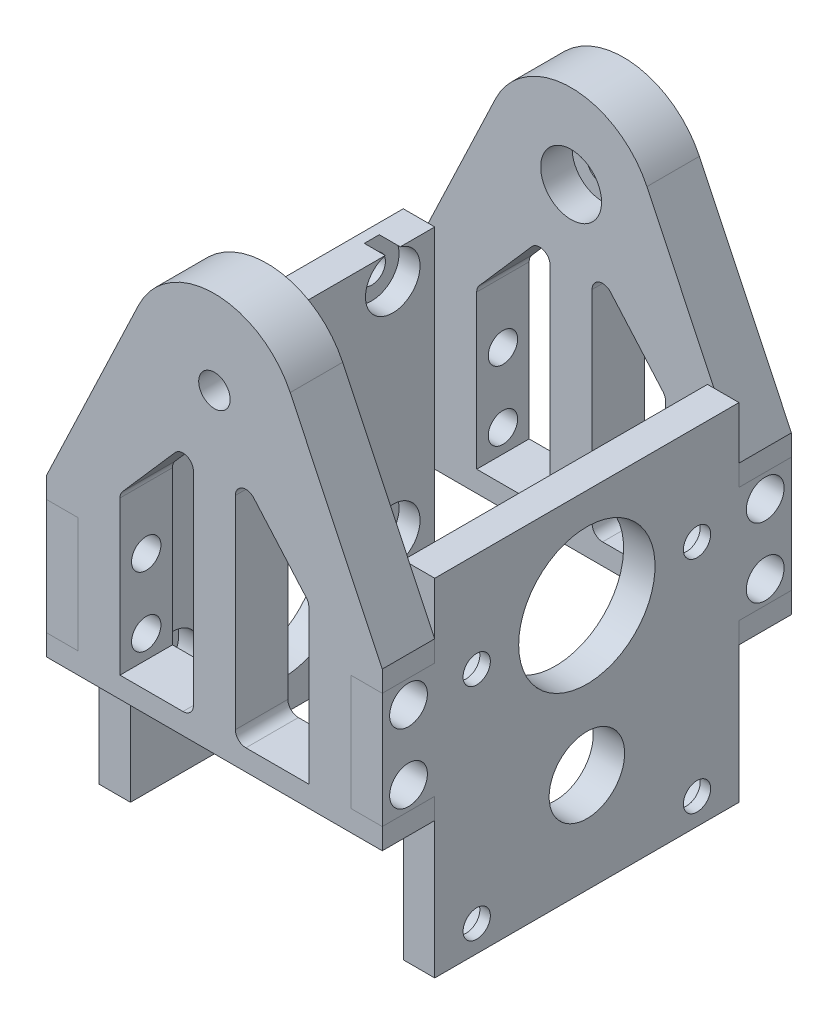
SolidWorks part; units mm, degrees
ref_plane "正面" through (0, 0, 0) normal (0, 0, 1) x (1, 0, 0)
ref_plane "平面" through (0, 0, 0) normal (0, 1, 0) x (1, 0, 0)
ref_plane "右側面" through (0, 0, 0) normal (1, 0, 0) x (0, 0, -1)
sketch "ｽｹｯﾁ1" plane through (0, 0, 0) normal (0, 0, 1) x (1, 0, 0)
  line L0 (-16, -15) -> (-16, -30)
  line L1 (-16, -30) -> (16, -30)
  line L2 (16, -30) -> (16, -15)
  line L3 (16, -15) -> (7.2234, 3.4383)
  line L4 (-7.2234, 3.4383) -> (-16, -15)
  line L5 (0, 0) -> (0, -30) construction
  line L6 (-16, -15) -> (16, -15) construction
  circle A0 centre (0, 0) radius 2.9
  arc A1 (7.2234, 3.4383) -> (-7.2234, 3.4383) centre (0, 0) ccw
  dimension "D1" = 5.8
  dimension "D6" = 8
  dimension "D2" = 16
  dimension "D3" = 16
  dimension "D4" = 15
  dimension "D5" = 15
extrude "ﾎﾞｽ - 押し出し1" add sketch "ｽｹｯﾁ1" along normal blind 3
sketch "ｽｹｯﾁ2" plane through (0, 0, 0) normal (0, 0, -1) x (-1, 0, 0)
  line L5 (16, -15) -> (7.2234, 3.4383)
  line L6 (-7.2234, 3.4383) -> (-16, -15)
  line L7 (-16, -15) -> (-16, -30)
  line L8 (-16, -30) -> (16, -30)
  line L9 (16, -30) -> (16, -15)
  line L10 (16, -15) -> (7.2234, 3.4383)
  line L11 (-7.2234, 3.4383) -> (-16, -15)
  line L12 (-16, -15) -> (-16, -30)
  line L13 (-16, -30) -> (16, -30)
  line L14 (16, -30) -> (16, -15)
  arc A1 (7.2234, 3.4383) -> (-7.2234, 3.4383) centre (0, 0) ccw
  arc A2 (7.2234, 3.4383) -> (-7.2234, 3.4383) centre (0, 0) ccw
  dimension "D1" = 0
extrude "ﾎﾞｽ - 押し出し2" add sketch "ｽｹｯﾁ2" along normal blind 2
ref_plane "平面1" through (0, 0, 33.5) normal (0, 0, 1) x (1, 0, 0)
sketch "ｽｹｯﾁ3" plane through (0, 0, 33.5) normal (0, 0, 1) x (1, 0, 0)
  line L5 (-7.2234, 3.4383) -> (-16, -15)
  line L6 (-16, -15) -> (-16, -30)
  line L7 (-16, -30) -> (16, -30)
  line L8 (16, -30) -> (16, -15)
  line L9 (16, -15) -> (7.2234, 3.4383)
  line L10 (-7.2234, 3.4383) -> (-16, -15)
  line L11 (-16, -15) -> (-16, -30)
  line L12 (-16, -30) -> (16, -30)
  line L13 (16, -30) -> (16, -15)
  line L14 (16, -15) -> (7.2234, 3.4383)
  circle A0 centre (0, 0) radius 2.9 construction
  arc A1 (7.2234, 3.4383) -> (-7.2234, 3.4383) centre (0, 0) ccw
  arc A2 (7.2234, 3.4383) -> (-7.2234, 3.4383) centre (0, 0) ccw
  circle A3 centre (0, 0) radius 2.9 construction
  circle A4 centre (0, 0) radius 3.6
  dimension "D2" = 7.2
  dimension "D1" = 0
extrude "ﾎﾞｽ - 押し出し3" add sketch "ｽｹｯﾁ3" against normal blind 1.5 separate body
sketch "ｽｹｯﾁ4" plane through (0, 0, 33.5) normal (0, 0, 1) x (1, 0, 0)
  line L5 (-7.2234, 3.4383) -> (-16, -15)
  line L6 (-16, -15) -> (-16, -30)
  line L7 (-16, -30) -> (16, -30)
  line L8 (16, -30) -> (16, -15)
  line L9 (16, -15) -> (7.2234, 3.4383)
  line L10 (-7.2234, 3.4383) -> (-16, -15)
  line L11 (-16, -15) -> (-16, -30)
  line L12 (-16, -30) -> (16, -30)
  line L13 (16, -30) -> (16, -15)
  line L14 (16, -15) -> (7.2234, 3.4383)
  arc A1 (7.2234, 3.4383) -> (-7.2234, 3.4383) centre (0, 0) ccw
  arc A2 (7.2234, 3.4383) -> (-7.2234, 3.4383) centre (0, 0) ccw
  dimension "D1" = 0
extrude "ﾎﾞｽ - 押し出し4" add sketch "ｽｹｯﾁ4" along normal blind 3.5
sketch "ｽｹｯﾁ5" plane through (0, 0, -2) normal (0, 0, -1) x (-1, 0, 0)
  line L0 (-16, -15) -> (-16, -30) construction
  line L1 (-16, -17) -> (-13, -17)
  line L2 (-16, -17) -> (-16, -28)
  line L3 (-16, -28) -> (-13, -28)
  line L4 (-13, -17) -> (-13, -28)
  line L5 (-16, -17) -> (-13, -28) construction
  line L6 (-16, -28) -> (-13, -17) construction
  line L7 (16, -30) -> (16, -15) construction
  line L8 (16, -17) -> (13, -17)
  line L9 (16, -17) -> (16, -28)
  line L10 (16, -28) -> (13, -28)
  line L11 (13, -17) -> (13, -28)
  line L12 (16, -17) -> (13, -28) construction
  line L13 (16, -28) -> (13, -17) construction
  line L14 (-16, -30) -> (16, -30) construction
  line L15 (-16, -15) -> (16, -15) construction
  line L16 (-7.2234, 3.4383) -> (-16, -15) construction
  point P4 (-14.5, -22.5)
  point P11 (14.5, -22.5)
  dimension "D1" = 3
  dimension "D2" = 3
  dimension "D3" = 2
  dimension "D4" = 2
extrude "ｶｯﾄ - 押し出し1" cut sketch "ｽｹｯﾁ5" against normal through all
sketch "ｽｹｯﾁ6" plane through (13, 0, 0) normal (1, 0, 0) x (0, 0, -1)
  line L0 (2, -17) -> (-3, -17)
  line L1 (-3, -17) -> (-3, -10)
  line L2 (-3, -10) -> (-32, -10)
  line L3 (-32, -15) -> (-32, 3.4383) construction
  line L4 (-32, -10) -> (-32, -17)
  line L5 (-32, -17) -> (-37, -17)
  line L6 (-37, -17) -> (-37, -28)
  line L7 (-37, -28) -> (-32, -28)
  line L8 (-32, -28) -> (-32, -43)
  line L9 (-32, -43) -> (-3, -43)
  line L10 (-3, -43) -> (-3, -28)
  line L11 (-3, -28) -> (2, -28)
  line L12 (2, -28) -> (2, -17)
  line L13 (-17.5, -10) -> (-17.5, -43) construction
  line L14 (0, 0) -> (-33.5, 0) construction
  line L15 (-7, -40.5) -> (-28, -40.5) construction
  line L16 (-7, -40.5) -> (-7, -19.5) construction
  line L17 (-7, -19.5) -> (-28, -19.5) construction
  line L18 (-28, -40.5) -> (-28, -19.5) construction
  line L19 (-7, -40.5) -> (-28, -19.5) construction
  line L20 (-7, -19.5) -> (-28, -40.5) construction
  line L21 (-33.5, 3.19) -> (-33.5, -3.19) construction
  line L22 (2, -26.5) -> (-37, -26.5) construction
  circle A0 centre (-17.5, -19.5) radius 6.5
  circle A1 centre (-28, -19.5) radius 1.3
  circle A2 centre (-7, -19.5) radius 1.3
  circle A3 centre (-28, -40.5) radius 1.3
  circle A4 centre (-7, -40.5) radius 1.3
  circle A5 centre (-17.5, -33.5) radius 6.5 construction
  circle A6 centre (-17.5, -33.5) radius 3.6
  point P24 (-17.5, -30)
  point P43 (-17.5, -26.5)
  dimension "D6" = 2.6
  dimension "D8" = 13
  dimension "D10" = 7.2
  dimension "D1" = 21
  dimension "D2" = 21
  dimension "D3" = 14.5
  dimension "D4" = 13
  dimension "D5" = 21
  dimension "D7" = 20
  dimension "D9" = 30
extrude "ﾎﾞｽ - 押し出し5" add sketch "ｽｹｯﾁ6" along normal up to surface (3 mm away) separate body up to face at (16, -16, 0.5)
sketch "ｽｹｯﾁ8" plane through (-13, 0, 0) normal (-1, 0, 0) x (0, 0, 1)
  line L0 (3, -10) -> (3, -43) construction
  line L1 (32, -10) -> (32, -43) construction
  line L2 (3, -26.5) -> (32, -26.5) construction
  line L12 (-2, -17) -> (-2, -28)
  line L13 (-2, -28) -> (3, -28)
  line L14 (3, -28) -> (3, -43)
  line L15 (3, -43) -> (32, -43)
  line L16 (32, -43) -> (32, -28)
  line L17 (32, -28) -> (37, -28)
  line L18 (37, -28) -> (37, -17)
  line L19 (37, -17) -> (32, -17)
  line L20 (32, -17) -> (32, -10)
  line L21 (32, -10) -> (3, -10)
  line L22 (3, -10) -> (3, -17)
  line L23 (3, -17) -> (-2, -17)
  line L24 (-2, -17) -> (-2, -28)
  line L25 (-2, -28) -> (3, -28)
  line L26 (3, -28) -> (3, -43)
  line L27 (3, -43) -> (32, -43)
  line L28 (32, -43) -> (32, -28)
  line L29 (32, -28) -> (37, -28)
  line L30 (37, -28) -> (37, -17)
  line L31 (37, -17) -> (32, -17)
  line L32 (32, -17) -> (32, -10)
  line L33 (32, -10) -> (3, -10)
  line L34 (3, -10) -> (3, -17)
  line L35 (3, -17) -> (-2, -17)
  circle A0 centre (28, -40.5) radius 1.3 construction
  circle A1 centre (28, -19.5) radius 1.3 construction
  circle A2 centre (7, -40.5) radius 1.3 construction
  circle A3 centre (17.5, -19.5) radius 6.5 construction
  circle A4 centre (7, -19.5) radius 1.3 construction
  circle A5 centre (28, -40.5) radius 1.3 construction
  circle A6 centre (28, -19.5) radius 1.3 construction
  circle A7 centre (7, -40.5) radius 1.3 construction
  circle A8 centre (17.5, -19.5) radius 6.5 construction
  circle A9 centre (7, -19.5) radius 1.3 construction
  circle A10 centre (28, -12.5) radius 1.3
  circle A11 centre (7, -12.5) radius 1.3
  circle A12 centre (28, -33.5) radius 1.3
  circle A13 centre (17.5, -33.5) radius 6.5
  circle A14 centre (7, -33.5) radius 1.3
  circle A15 centre (17.5, -19.5) radius 3.6
  dimension "D2" = 7.2
  dimension "D1" = 0
extrude "ﾎﾞｽ - 押し出し6" add sketch "ｽｹｯﾁ8" along normal up to surface (3 mm away) separate body up to face at (-16, -29, 0.5)
sketch "ｽｹｯﾁ7" plane through (0, 0, -2) normal (0, 0, -1) x (-1, 0, 0)
  line L0 (0, 0) -> (0, -16.5) construction
  line L1 (-16, -30) -> (16, -30) construction
  line L2 (9, -28) -> (-9, -28) construction
  line L3 (9, -28) -> (9, -5) construction
  line L4 (9, -5) -> (-9, -5) construction
  line L5 (-9, -28) -> (-9, -5) construction
  line L6 (9, -28) -> (-9, -5) construction
  line L7 (9, -5) -> (-9, -28) construction
  line L8 (-13, -28) -> (-13, -17) construction
  line L9 (-9, -28) -> (-3, -28)
  line L10 (-2, -27) -> (-2, -7.6614)
  line L11 (-3.7526, -7.0029) -> (-8.7526, -12.7172)
  line L12 (-9, -13.3757) -> (-9, -28)
  line L15 (-16, -17) -> (-13, -17) construction
  line L16 (9, -28) -> (3, -28)
  line L17 (9, -13.3757) -> (9, -28)
  line L18 (3.7526, -7.0029) -> (8.7526, -12.7172)
  line L19 (2, -27) -> (2, -7.6614)
  circle A0 centre (0, 0) radius 1.5
  arc A2 (3, -28) -> (2, -27) centre (3, -27) cw
  arc A3 (-3, -28) -> (-2, -27) centre (-3, -27) ccw
  arc A5 (-2, -7.6614) -> (-3.7526, -7.0029) centre (-3, -7.6614) ccw
  arc A6 (3.7526, -7.0029) -> (2, -7.6614) centre (3, -7.6614) ccw
  arc A7 (9, -13.3757) -> (8.7526, -12.7172) centre (8, -13.3757) ccw
  arc A8 (-8.7526, -12.7172) -> (-9, -13.3757) centre (-8, -13.3757) ccw
  point P28 (2, -28)
  point P31 (-2, -28)
  point P37 (-2, -5)
  point P40 (2, -5)
  point P43 (9, -13)
  point P46 (-9, -13)
  dimension "D1" = 3
  dimension "D8" = 1
  dimension "D2" = 2
  dimension "D3" = 4
  dimension "D4" = 23
  dimension "D5" = 4
  dimension "D6" = 7
extrude "ｶｯﾄ - 押し出し2" cut sketch "ｽｹｯﾁ7" against normal through all
sketch "ｽｹｯﾁ10" plane through (16, 0, 0) normal (1, 0, 0) x (0, 0, -1)
  line L4 (-34.5, -15) -> (-34.5, -30) construction
  line L5 (-32, -15) -> (-37, -15) construction
  line L6 (-32, -30) -> (-37, -30) construction
  line L8 (-0.5, -15) -> (-0.5, -30) construction
  line L9 (-3, -15) -> (2, -15) construction
  line L10 (-3, -30) -> (2, -30) construction
  line L11 (-37, -17) -> (-32, -17) construction
  line L14 (-32, -28) -> (-37, -28) construction
  line L15 (-3, -17) -> (2, -17) construction
  line L16 (2, -28) -> (-3, -28) construction
  point P26 (-34.5, -19.2)
  point P28 (-34.5, -25.8)
  point P30 (-0.5, -19.2)
  point P32 (-0.5, -25.8)
  dimension "D1" = 2.2
  dimension "D2" = 2.2
  dimension "D3" = 2.2
  dimension "D4" = 2.2
hole_wizard "Ø2.8 (2.8) 直径の穴1" positions "ｽｹｯﾁ10" profile "ｽｹｯﾁ11" hole size "Ø2.8" standard "JIS"
sketch "ｽｹｯﾁ11" plane through (16, -25.8, 0.5) normal (0, 1, 0) x (0, 0, -1)
  line L0 (0, 0) -> (0, 14)
  line L1 (0, 14) -> (1.4, 13.1588)
  line L2 (1.4, 13.1588) -> (1.4, 0)
  line L5 (1.4, 0) -> (0, 0)
  line L10 (0, 14) -> (-1.4, 13.1588) construction
  line L11 (0, -6.35) -> (0, 107.95) construction
  dimension "穴の直径" = 2.8
  dimension "穴の深さ" = 14
  dimension "ﾄﾞﾘﾙ角度" = 118
hole_wizard "Ø2.8 (2.8) 直径の穴2" positions "ｽｹｯﾁ12" profile "ｽｹｯﾁ13" hole size "Ø2.8" standard "JIS"
sketch "ｽｹｯﾁ12" plane through (-16, 0, 0) normal (-1, 0, 0) x (0, 0, 1)
  point P0 (34.5, -19.2)
  point P3 (34.5, -25.8)
  point P6 (0.5, -19.2)
  point P9 (0.5, -25.8)
sketch "ｽｹｯﾁ13" plane through (-16, -19.2, 34.5) normal (0, 1, 0) x (0, 0, 1)
  line L0 (0, 0) -> (0, 14)
  line L1 (0, 14) -> (1.4, 13.1588)
  line L2 (1.4, 13.1588) -> (1.4, 0)
  line L5 (1.4, 0) -> (0, 0)
  line L10 (0, 14) -> (-1.4, 13.1588) construction
  line L11 (0, -6.35) -> (0, 107.95) construction
  dimension "穴の直径" = 2.8
  dimension "穴の深さ" = 14
  dimension "ﾄﾞﾘﾙ角度" = 118
hole_wizard "Ø3.6 (3.6) 直径の穴1" positions "ｽｹｯﾁ14" profile "ｽｹｯﾁ16" hole size "Ø3.6" standard "JIS" end condition through all
sketch "ｽｹｯﾁ14" plane through (16, 0, 0) normal (1, 0, 0) x (0, 0, -1)
  point P0 (-34.5, -19.2)
  point P3 (-34.5, -25.8)
  point P6 (-0.5, -19.2)
  point P9 (-0.5, -25.8)
sketch "ｽｹｯﾁ16" plane through (16, -19.2, 34.5) normal (0, 1, 0) x (0, 0, -1)
  line L0 (0, 0) -> (0, 32)
  line L1 (0, 32) -> (1.8, 32)
  line L2 (1.8, 32) -> (1.8, 0)
  line L5 (1.8, 0) -> (0, 0)
  line L11 (0, -6.35) -> (0, 107.95) construction
  dimension "通し穴の直径" = 3.6
  dimension "通し穴の深さ" = 32
sketch "ｽｹｯﾁ17" plane through (13, 0, 0) normal (-1, 0, 0) x (0, 0, 1)
  circle A0 centre (28, -40.5) radius 1.3 construction
  circle A1 centre (7, -40.5) radius 1.3 construction
  circle A2 centre (28, -19.5) radius 1.3 construction
  circle A3 centre (7, -19.5) radius 1.3 construction
  circle A4 centre (28, -40.5) radius 1.3 construction
  circle A5 centre (7, -40.5) radius 1.3 construction
  circle A6 centre (28, -19.5) radius 1.3 construction
  circle A7 centre (7, -19.5) radius 1.3 construction
  circle A8 centre (7, -19.5) radius 2.6
  circle A9 centre (7, -40.5) radius 2.6
  circle A10 centre (28, -40.5) radius 2.6
  circle A11 centre (28, -19.5) radius 2.6
  dimension "D1" = 5.2
extrude "ｶｯﾄ - 押し出し4" cut sketch "ｽｹｯﾁ17" against normal blind 2
sketch "ｽｹｯﾁ18" plane through (-13, 0, 0) normal (1, 0, 0) x (0, 0, -1)
  circle A0 centre (-28, -33.5) radius 1.3 construction
  circle A1 centre (-28, -12.5) radius 1.3 construction
  circle A2 centre (-7, -12.5) radius 1.3 construction
  circle A3 centre (-28, -33.5) radius 1.3 construction
  circle A4 centre (-28, -12.5) radius 1.3 construction
  circle A5 centre (-7, -12.5) radius 1.3 construction
  circle A6 centre (-7, -33.5) radius 1.3 construction
  circle A7 centre (-7, -33.5) radius 1.3 construction
  circle A8 centre (-28, -12.5) radius 2.6
  circle A9 centre (-28, -33.5) radius 2.6
  circle A10 centre (-7, -33.5) radius 2.6
  circle A11 centre (-7, -12.5) radius 2.6
  dimension "D1" = 5.2
extrude "ｶｯﾄ - 押し出し5" cut sketch "ｽｹｯﾁ18" against normal blind 2
equation "\"D2@ｽｹｯﾁ5\"=\"D1@ｽｹｯﾁ5\""
equation "\"D8@ｽｹｯﾁ6\"=12.5+0.5"
equation "\"D1@ｽｹｯﾁ10\"=\"D2@ｽｹｯﾁ10\""
equation "\"D3@ｽｹｯﾁ10\"=\"D2@ｽｹｯﾁ10\""
equation "\"D4@ｽｹｯﾁ10\"=\"D2@ｽｹｯﾁ10\""
